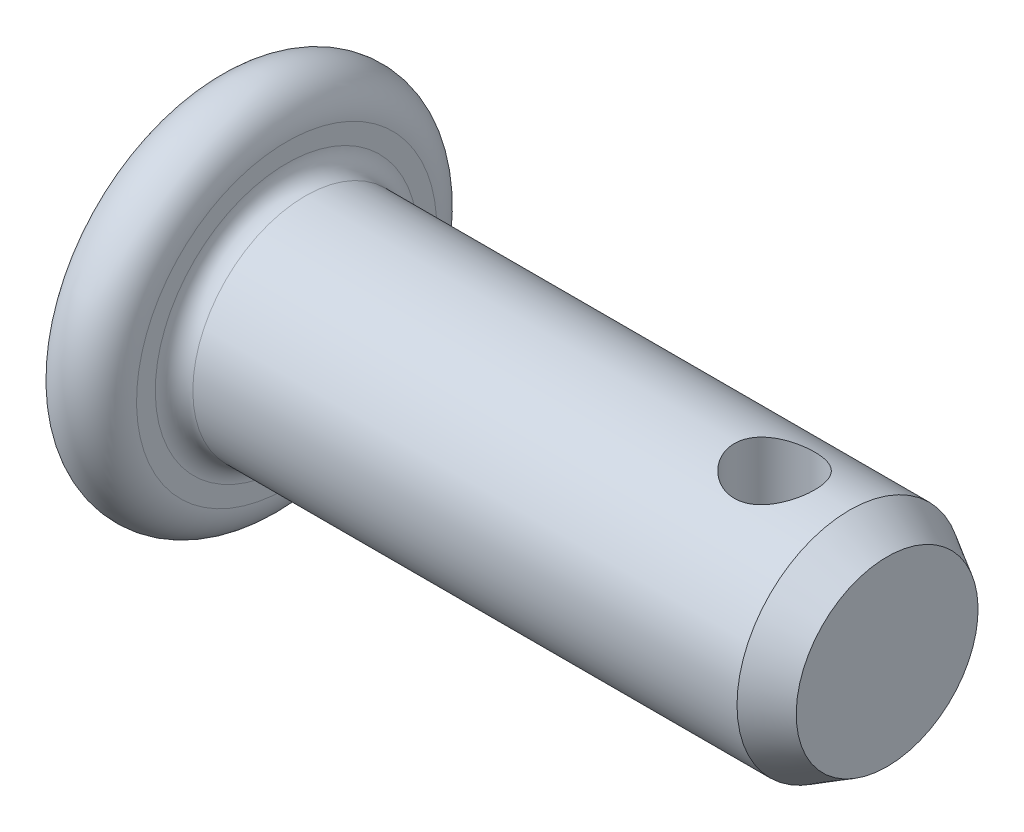
SolidWorks part; units mm, degrees
ref_plane "Front" through (0, 0, 0) normal (0, 0, 1) x (1, 0, 0)
ref_plane "Top" through (0, 0, 0) normal (0, 1, 0) x (1, 0, 0)
ref_plane "Right" through (0, 0, 0) normal (1, 0, 0) x (0, 0, -1)
sketch "Sketch1" plane through (0, 0, 0) normal (0, 0, 1) x (1, 0, 0)
  line L0 (18, 0) -> (0, 0)
  line L1 (0, 0) -> (0, 4)
  line L2 (18, 0) -> (18, 2.4226)
  line L3 (18, 2.4226) -> (17, 3)
  line L4 (17, 3) -> (2, 3)
  line L5 (2, 3) -> (2, 4)
  line L6 (-19.83, 0) -> (9.2989, 0) construction
  arc A0 (0, 4) -> (2, 4) centre (1, 4) cw
  dimension "l" = 16
  dimension "k" = 2
  dimension "d" = 6
  dimension "D4" = 30
  dimension "c" = 1
  dimension "dk" = 10
revolve "BaseBody" add sketch "Sketch1" angle 360 about L6
fillet "Chamfer1" radius 0.5 1 edges at (2, -3, 0)
sketch "Sketch2" plane through (0, 0, 0) normal (0, 1, 0) x (1, 0, 0)
  line L0 (-19.83, 0) -> (9.2989, 0) construction
  line L1 (18, -2.4226) -> (18, 2.4226) construction
  circle A0 centre (15, 0) radius 1.07
  dimension "D2" = 3
  dimension "d1" = 2.14
extrude "Hole" cut sketch "Sketch2" against normal through all and the other way through all
ref_axis "基准轴1" through (17, 0, 0) along (-1, 0, 0)
ref_axis "基准轴2" through (15, -3, 0) along (0, 1, 0)
ref_plane "基准面1" through (0, 0, 0) normal (0, 1, 0) x (1, 0, 0)
